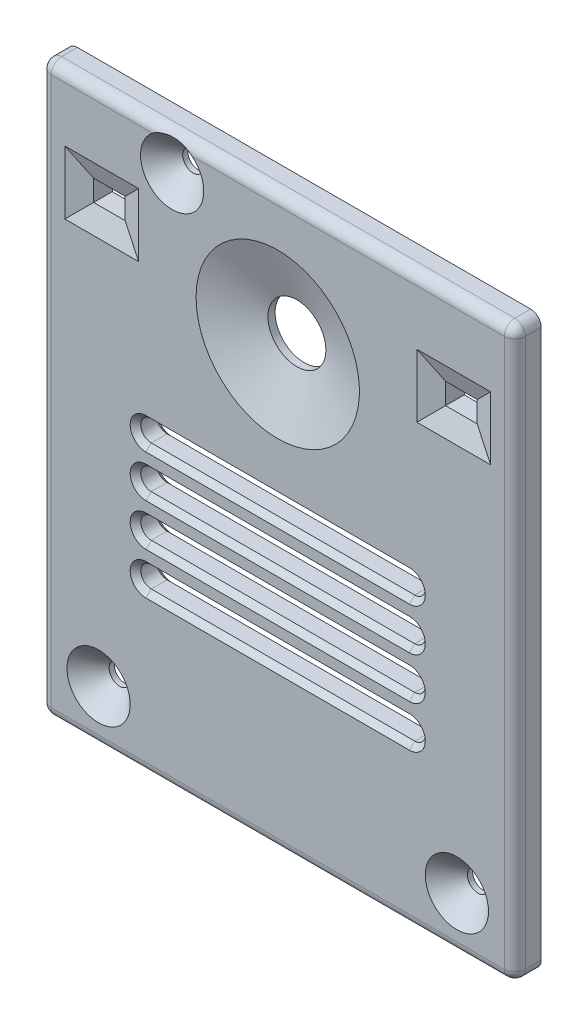
SolidWorks part; units mm, degrees
ref_plane "Front Plane" through (0, 0, 0) normal (0, 0, 1) x (1, 0, 0)
ref_plane "Top Plane" through (0, 0, 0) normal (0, 1, 0) x (1, 0, 0)
ref_plane "Right Plane" through (0, 0, 0) normal (1, 0, 0) x (0, 0, -1)
sketch "Sketch1" plane through (0, 0, 0) normal (0, 0, 1) x (1, 0, 0)
  line L1 (21.5, -27) -> (-21.5, -27)
  line L2 (22.5, -26) -> (22.5, 26)
  line L3 (21.5, 27) -> (-21.5, 27)
  line L4 (-22.5, -26) -> (-22.5, 26)
  line L5 (22.5, -27) -> (-22.5, 27) construction
  line L6 (22.5, 27) -> (-22.5, -27) construction
  circle A0 centre (-10.0184, 23.665) radius 1
  circle A1 centre (-17, -22) radius 1
  circle A2 centre (17, -22) radius 1
  arc A3 (-21.5, -27) -> (-22.5, -26) centre (-21.5, -26) cw
  arc A4 (21.5, -27) -> (22.5, -26) centre (21.5, -26) ccw
  arc A5 (22.5, 26) -> (21.5, 27) centre (21.5, 26) ccw
  arc A6 (-21.5, 27) -> (-22.5, 26) centre (-21.5, 26) ccw
  point P0 (0, 0)
  dimension "D1" = 1
extrude "Boss-Extrude1" add sketch "Sketch1" along normal blind 2.5
sketch "Sketch2" plane through (0, 0, 2.5) normal (0, 0, 1) x (1, 0, 0)
  line L0 (-22.5, 26) -> (-22.5, -26) construction
  line L1 (21.5, 27) -> (-21.5, 27) construction
  circle A0 centre (0, 14.6) radius 2.75
  dimension "D1" = 5.5
  dimension "D2" = 22.5
  dimension "D3" = 12.4
extrude "Cut-Extrude1" cut sketch "Sketch2" against normal blind 2.5
chamfer "Chamfer1" distance 5 angle 20 1 edges at (2.75, 14.6, 2.5) first distance on face at (2.75, 14.6, 2.5)
sketch "Sketch3" plane through (0, 0, 2.5) normal (0, 0, 1) x (1, 0, 0)
  line L0 (-12.5, 1) -> (12.5, 1) construction
  line L1 (-12.5, 2) -> (12.5, 2)
  line L2 (-12.5, 0) -> (12.5, 0)
  line L3 (-12.5, -3) -> (12.5, -3) construction
  line L4 (-12.5, -2) -> (12.5, -2)
  line L5 (-12.5, -4) -> (12.5, -4)
  line L6 (-12.5, -7) -> (12.5, -7) construction
  line L7 (-12.5, -6) -> (12.5, -6)
  line L8 (-12.5, -8) -> (12.5, -8)
  line L9 (-12.5, -11) -> (12.5, -11) construction
  line L10 (-12.5, -10) -> (12.5, -10)
  line L11 (-12.5, -12) -> (12.5, -12)
  arc A0 (-12.5, 2) -> (-12.5, 0) centre (-12.5, 1) ccw
  arc A1 (12.5, 0) -> (12.5, 2) centre (12.5, 1) ccw
  arc A2 (-12.5, -2) -> (-12.5, -4) centre (-12.5, -3) ccw
  arc A3 (12.5, -4) -> (12.5, -2) centre (12.5, -3) ccw
  arc A4 (-12.5, -6) -> (-12.5, -8) centre (-12.5, -7) ccw
  arc A5 (12.5, -8) -> (12.5, -6) centre (12.5, -7) ccw
  arc A6 (-12.5, -10) -> (-12.5, -12) centre (-12.5, -11) ccw
  arc A7 (12.5, -12) -> (12.5, -10) centre (12.5, -11) ccw
  point P2 (0, 1)
  point P9 (0, -3)
  point P15 (0, -7)
  point P22 (0, -11)
  dimension "D1" = 25
  dimension "D2" = 12.5
  dimension "D3" = 2
  dimension "D5" = 25
  dimension "D6" = 2
  dimension "D7" = 4
  dimension "D8" = 2
  dimension "D9" = 25
  dimension "D10" = 4
  dimension "D11" = 2
  dimension "D12" = 25
  dimension "D13" = 4
extrude "Cut-Extrude2" cut sketch "Sketch3" against normal blind 2.5
chamfer "Chamfer2" distance 0.5 angle 45 32 edges at (0, -12, 0) (13.5, -11, 0) (-13.5, -11, 0) (0, -10, 0) (0, -6, 0) (-13.5, -7, 0) (13.5, -7, 0) (0, -8, 0) (0, -4, 0) (13.5, -3, 0) (-13.5, -3, 0) (0, -2, 0) (0, 0, 0) (13.5, 1, 0) (-13.5, 1, 0) (0, 2, 0) (0, -12, 2.5) (13.5, -11, 2.5) (-13.5, -11, 2.5) (0, -10, 2.5) (0, -8, 2.5) (13.5, -7, 2.5) (-13.5, -7, 2.5) (0, -6, 2.5) (0, -4, 2.5) (13.5, -3, 2.5) (-13.5, -3, 2.5) (0, -2, 2.5) (0, 0, 2.5) (13.5, 1, 2.5) (-13.5, 1, 2.5) (0, 2, 2.5)
chamfer "Chamfer3" distance 2 angle 45 3 edges at (-9.0184, 23.665, 2.5) (18, -22, 2.5) (-16, -22, 2.5)
sketch "Sketch4" plane through (0, 0, 2.5) normal (0, 0, 1) x (1, 0, 0)
  line L0 (-22.5, 26) -> (-22.5, -26) construction
  line L1 (-18.2, 18.8) -> (-15.2, 18.8)
  line L2 (-18.2, 18.8) -> (-18.2, 16.8)
  line L3 (-18.2, 16.8) -> (-15.2, 16.8)
  line L4 (-15.2, 18.8) -> (-15.2, 16.8)
  line L5 (-18.2, 18.8) -> (-15.2, 16.8) construction
  line L6 (-18.2, 16.8) -> (-15.2, 18.8) construction
  line L7 (15.2, 16.8) -> (18.2, 16.8)
  line L8 (15.2, 16.8) -> (15.2, 18.8)
  line L9 (15.2, 18.8) -> (18.2, 18.8)
  line L10 (18.2, 16.8) -> (18.2, 18.8)
  line L11 (15.2, 16.8) -> (18.2, 18.8) construction
  line L12 (15.2, 18.8) -> (18.2, 16.8) construction
  line L13 (21.5, 27) -> (-21.5, 27) construction
  line L14 (22.5, -26) -> (22.5, 26) construction
  point P0 (-16.7, 17.8)
  point P5 (16.7, 17.8)
  dimension "D6" = 2
  dimension "D2" = 2
  dimension "D3" = 4.3
  dimension "D4" = 8.2
  dimension "D7" = 8.2
  dimension "D8" = 4.3
extrude "Cut-Extrude3" cut sketch "Sketch4" against normal blind 2.5
chamfer "Chamfer4" distance 2 angle 20 8 edges at (16.7, 16.8, 2.5) (18.2, 17.8, 2.5) (16.7, 18.8, 2.5) (15.2, 17.8, 2.5) (-18.2, 17.8, 2.5) (-16.7, 16.8, 2.5) (-15.2, 17.8, 2.5) (-16.7, 18.8, 2.5) first distance on face at (16.7, 17.8, 2.5)
fillet "Fillet1" radius 1 8 edges at (-22.2071, 26.7071, 2.5) (22.2071, 26.7071, 2.5) (22.2071, -26.7071, 2.5) (-22.2071, -26.7071, 2.5) (0, 27, 2.5) (22.5, 0, 2.5) (0, -27, 2.5) (-22.5, 0, 2.5)
equation "\"D5@Sketch3\"=\"D1@Sketch3\""
equation "\"D6@Sketch3\"=\"D3@Sketch3\""
equation "\"D9@Sketch3\"=\"D1@Sketch3\""
equation "\"D8@Sketch3\"=\"D3@Sketch3\""
equation "\"D10@Sketch3\"=\"D7@Sketch3\""
equation "\"D11@Sketch3\"=\"D3@Sketch3\""
equation "\"D12@Sketch3\"=\"D1@Sketch3\""
equation "\"D13@Sketch3\"=\"D7@Sketch3\""
equation "\"D5@Sketch4\"=\"D1@Sketch4\""
equation "\"D6@Sketch4\"=\"D2@Sketch4\""
equation "\"D7@Sketch4\"=\"D4@Sketch4\""
equation "\"D8@Sketch4\"=\"D3@Sketch4\""
